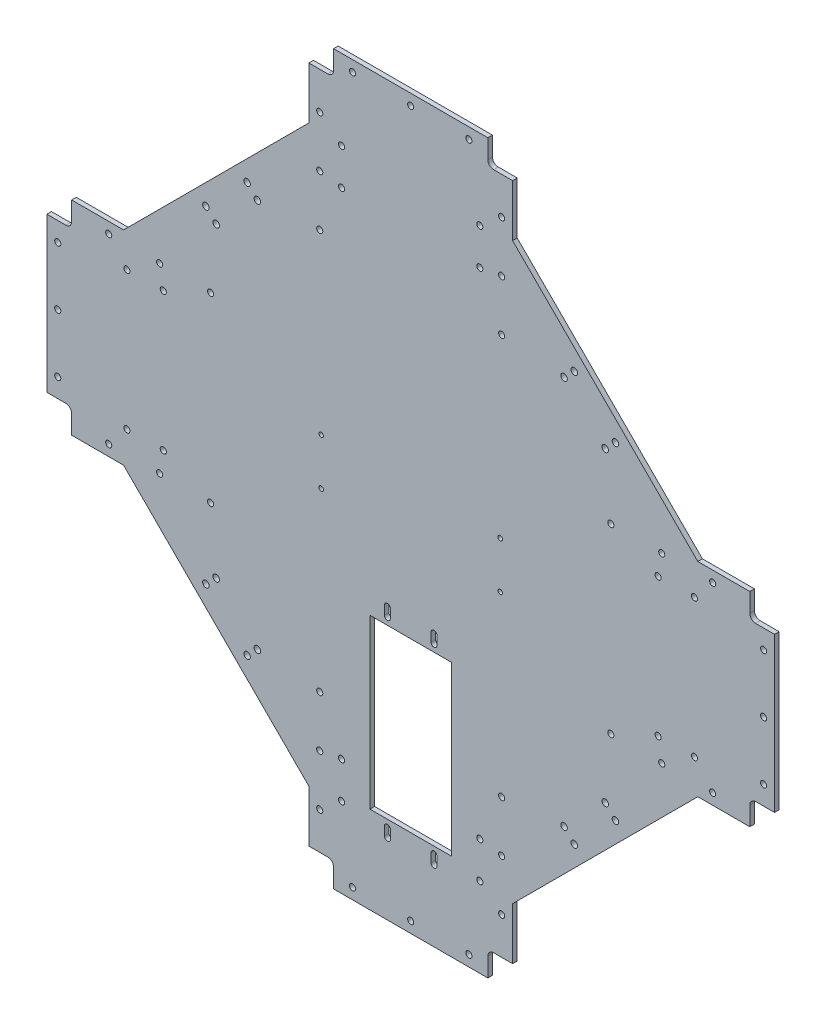
SolidWorks part; units mm, degrees
ref_plane "Front Plane" through (0, 0, 0) normal (0, 0, 1) x (1, 0, 0)
ref_plane "Top Plane" through (0, 0, 0) normal (0, 1, 0) x (1, 0, 0)
ref_plane "Right Plane" through (0, 0, 0) normal (1, 0, 0) x (0, 0, -1)
sketch "Sketch1" plane through (0, 0, 0) normal (0, 0, 1) x (1, 0, 0)
  line L0 (0, 0) -> (0, 180)
  line L1 (0, 180) -> (140, 180)
  line L2 (140, 180) -> (140, 0)
  line L3 (140, 0) -> (320, 0)
  line L4 (320, 0) -> (320, -140)
  line L5 (320, -140) -> (140, -140)
  line L6 (140, -140) -> (140, -320)
  line L7 (140, -320) -> (0, -320)
  line L8 (0, -320) -> (0, -140)
  line L9 (0, -140) -> (-180, -140)
  line L10 (-180, -140) -> (-180, 0)
  line L11 (-180, 0) -> (0, 0)
  line L12 (70, 180) -> (70, -320) construction
  line L13 (0, 180) -> (17, 180)
  line L14 (0, 180) -> (0, 163)
  line L15 (0, 163) -> (17, 163)
  line L16 (17, 180) -> (17, 163)
  line L17 (-180, -70) -> (320, -70) construction
  line L18 (140, 0) -> (0, -140) construction
  line L19 (0, 0) -> (140, -140) construction
  line L20 (7.5, 137.5) -> (7.5, 67.5) construction
  line L21 (140, 180) -> (123, 180)
  line L22 (140, 180) -> (140, 163)
  line L23 (140, 163) -> (123, 163)
  line L24 (123, 180) -> (123, 163)
  line L25 (-180, 0) -> (-163, 0)
  line L26 (-180, 0) -> (-180, -17)
  line L27 (-180, -17) -> (-163, -17)
  line L28 (-163, 0) -> (-163, -17)
  line L29 (-180, -140) -> (-163, -140)
  line L30 (-180, -140) -> (-180, -123)
  line L31 (-180, -123) -> (-163, -123)
  line L32 (-163, -140) -> (-163, -123)
  line L33 (320, 0) -> (303, 0)
  line L34 (320, 0) -> (320, -17)
  line L35 (320, -17) -> (303, -17)
  line L36 (303, 0) -> (303, -17)
  line L37 (320, -140) -> (303, -140)
  line L38 (320, -140) -> (320, -123)
  line L39 (320, -123) -> (303, -123)
  line L40 (303, -140) -> (303, -123)
  line L41 (140, -320) -> (123, -320)
  line L42 (140, -320) -> (140, -303)
  line L43 (140, -303) -> (123, -303)
  line L44 (123, -320) -> (123, -303)
  line L45 (0, -320) -> (17, -320)
  line L46 (0, -320) -> (0, -303)
  line L47 (0, -303) -> (17, -303)
  line L48 (17, -320) -> (17, -303)
  line L49 (22.5, 125) -> (117.5, 125) construction
  line L50 (22.5, 125) -> (22.5, 100) construction
  line L51 (22.5, 100) -> (117.5, 100) construction
  line L52 (117.5, 125) -> (117.5, 100) construction
  line L53 (30, 172.5) -> (110, 172.5) construction
  line L64 (42, -202.325) -> (98, -202.325) construction
  line L69 (42, -144.65) -> (98, -144.65)
  line L70 (42, -144.65) -> (42, -260)
  line L71 (42, -260) -> (98, -260)
  line L72 (98, -144.65) -> (98, -260)
  line L73 (51.95, -265) -> (56.05, -265) construction
  line L74 (51.95, -265) -> (51.95, -271)
  line L75 (51.95, -271) -> (56.05, -271) construction
  line L76 (56.05, -265) -> (56.05, -271)
  line L77 (88.05, -265) -> (88.05, -271)
  line L78 (83.95, -265) -> (83.95, -271)
  line L79 (88.05, -139.65) -> (88.05, -133.65)
  line L80 (83.95, -139.65) -> (83.95, -133.65)
  line L81 (51.95, -139.65) -> (51.95, -133.65)
  line L82 (56.05, -139.65) -> (56.05, -133.65)
  line L83 (8.5, -54) -> (131.5, -86) construction
  line L84 (8.5, -54) -> (131.5, -54) construction
  line L85 (8.5, -54) -> (8.5, -86) construction
  line L86 (8.5, -86) -> (131.5, -86) construction
  line L87 (131.5, -54) -> (131.5, -86) construction
  line L88 (131.5, -54) -> (8.5, -86) construction
  circle A0 centre (22.5, 125) radius 2.1
  circle A1 centre (22.5, 100) radius 2.1
  circle A2 centre (117.5, 125) radius 2.1
  circle A3 centre (117.5, 100) radius 2.1
  circle A4 centre (-100, -117.5) radius 2.1
  circle A5 centre (-125, -117.5) radius 2.1
  circle A6 centre (-100, -22.5) radius 2.1
  circle A7 centre (-125, -22.5) radius 2.1
  circle A8 centre (240, -117.5) radius 2.1
  circle A9 centre (240, -22.5) radius 2.1
  circle A10 centre (265, -22.5) radius 2.1
  circle A11 centre (265, -117.5) radius 2.1
  circle A12 centre (117.5, -265) radius 2.1
  circle A13 centre (117.5, -240) radius 2.1
  circle A14 centre (22.5, -240) radius 2.1
  circle A15 centre (22.5, -265) radius 2.1
  circle A17 centre (7.5, 137.5) radius 2.1
  circle A18 centre (7.5, 67.5) radius 2.1
  circle A19 centre (7.5, 102.5) radius 2.1
  circle A20 centre (30, 172.5) radius 2.1
  circle A21 centre (70, 172.5) radius 2.1
  circle A22 centre (110, 172.5) radius 2.1
  circle A23 centre (132.5, 67.5) radius 2.1
  circle A24 centre (132.5, 102.5) radius 2.1
  circle A25 centre (132.5, 137.5) radius 2.1
  circle A26 centre (207.5, -7.5) radius 2.1
  circle A27 centre (242.5, -7.5) radius 2.1
  circle A28 centre (277.5, -7.5) radius 2.1
  circle A29 centre (312.5, -30) radius 2.1
  circle A30 centre (312.5, -70) radius 2.1
  circle A31 centre (312.5, -110) radius 2.1
  circle A32 centre (277.5, -132.5) radius 2.1
  circle A33 centre (242.5, -132.5) radius 2.1
  circle A34 centre (207.5, -132.5) radius 2.1
  circle A35 centre (-67.5, -132.5) radius 2.1
  circle A36 centre (-102.5, -132.5) radius 2.1
  circle A37 centre (-137.5, -132.5) radius 2.1
  circle A38 centre (-172.5, -110) radius 2.1
  circle A39 centre (-172.5, -70) radius 2.1
  circle A40 centre (-172.5, -30) radius 2.1
  circle A41 centre (-137.5, -7.5) radius 2.1
  circle A42 centre (-102.5, -7.5) radius 2.1
  circle A43 centre (-67.5, -7.5) radius 2.1
  circle A44 centre (7.5, -207.5) radius 2.1
  circle A45 centre (7.5, -242.5) radius 2.1
  circle A46 centre (7.5, -277.5) radius 2.1
  circle A47 centre (30, -312.5) radius 2.1
  circle A48 centre (70, -312.5) radius 2.1
  circle A49 centre (110, -312.5) radius 2.1
  circle A50 centre (132.5, -277.5) radius 2.1
  circle A51 centre (132.5, -242.5) radius 2.1
  circle A52 centre (132.5, -207.5) radius 2.1
  arc A53 (51.95, -265) -> (56.05, -265) centre (54, -265) cw
  arc A54 (51.95, -271) -> (56.05, -271) centre (54, -271) ccw
  arc A55 (88.05, -271) -> (83.95, -271) centre (86, -271) cw
  arc A56 (88.05, -265) -> (83.95, -265) centre (86, -265) ccw
  arc A57 (88.05, -133.65) -> (83.95, -133.65) centre (86, -133.65) ccw
  arc A58 (88.05, -139.65) -> (83.95, -139.65) centre (86, -139.65) cw
  arc A59 (51.95, -133.65) -> (56.05, -133.65) centre (54, -133.65) cw
  arc A60 (51.95, -139.65) -> (56.05, -139.65) centre (54, -139.65) ccw
  circle A61 centre (8.5, -54) radius 1.55
  circle A62 centre (131.5, -54) radius 1.55
  circle A63 centre (131.5, -86) radius 1.55
  circle A64 centre (8.5, -86) radius 1.55
  point P21 (70, -320)
  point P24 (320, -70)
  point P147 (70, -144.65)
  point P197 (70, -70)
  point P198 (70, -70)
  dimension "D29" = 4.2
  dimension "D30" = 4.2
  dimension "D31" = 4.2
  dimension "D32" = 4.2
  dimension "D33" = 4.2
  dimension "D34" = 4.2
  dimension "D35" = 4.2
  dimension "D42" = 4.2
  dimension "D43" = 4.2
  dimension "D44" = 4.2
  dimension "D59" = 3.1
  dimension "D60" = 3.1
  dimension "D61" = 3.1
  dimension "D62" = 3.1
  dimension "D1" = 140
  dimension "D2" = 140
  dimension "D3" = 140
  dimension "D4" = 140
  dimension "D5" = 180
  dimension "D6" = 180
  dimension "D7" = 180
  dimension "D8" = 180
  dimension "D9" = 17
  dimension "D10" = 17
  dimension "D11" = 17
  dimension "D12" = 17
  dimension "D13" = 17
  dimension "D14" = 17
  dimension "D15" = 17
  dimension "D16" = 17
  dimension "D17" = 17
  dimension "D18" = 17
  dimension "D19" = 17
  dimension "D20" = 17
  dimension "D21" = 17
  dimension "D22" = 17
  dimension "D23" = 17
  dimension "D24" = 17
  dimension "D25" = 95
  dimension "D26" = 25
  dimension "D27" = 22.5
  dimension "D28" = 55
  dimension "D36" = 42.5
  dimension "D37" = 70
  dimension "D38" = 7.5
  dimension "D39" = 80
  dimension "D40" = 30
  dimension "D41" = 7.5
  dimension "D49" = 56
  dimension "D51" = 20
  dimension "D52" = 115.35
  dimension "D53" = 5
  dimension "D54" = 16
  dimension "D55" = 4.1
  dimension "D56" = 6
  dimension "D57" = 123
  dimension "D58" = 32
extrude "Boss-Extrude1" add sketch "Sketch1" along normal blind 3.175 contours L48 L7 L44 L43 L6 L5 L40 L39 L4 L35 L36 L3 L2 L23 L24 L1 L16 L15 L0 L11 L28 L27 L10 L31 L32 L9 L8 L47 A52 A51 A50 A48 A46 A44 A42 A40 A38 A37 A36 region at (70, -62.0997, 0)
fillet "Fillet1" radius 4 12 edges at (17, 163, 1.5875) (0, 0, 1.5875) (-163, -17, 1.5875) (-163, -123, 1.5875) (0, -140, 1.5875) (17, -303, 1.5875) (123, -303, 1.5875) (140, -140, 1.5875) (303, -123, 1.5875) (303, -17, 1.5875) (140, 0, 1.5875) (123, 163, 1.5875)
ref_point "Point1"
ref_plane "Plane1" through (0, 0, 0) normal (0, 0, 1) x (0, -1, 0)
sketch "Sketch10" plane through (0, 0, 0) normal (0, 0, 1) x (1, 0, 0)
  line L0 (-127.2792, -140) -> (0, -267.2792)
  line L1 (-4, -140) -> (-163, -140) construction
  line L2 (0, -1.7463) -> (0, 1.7463) construction
  line L4 (0, -140) -> (-63.6396, -203.6396) construction
  line L6 (-127.2792, -140) -> (0, -140)
  line L7 (0, -140) -> (0, -267.2792)
  line L8 (-70.7107, -182.4264) -> (-42.4264, -210.7107) construction
  circle A0 centre (-70.7107, -182.4264) radius 2.25
  circle A1 centre (-42.4264, -210.7107) radius 2.25
  circle A2 centre (-63.6396, -175.3553) radius 2.25
  circle A3 centre (-35.3553, -203.6396) radius 2.25
  point P11 (-56.5685, -196.5685)
  dimension "D6" = 2
  dimension "D4" = 4.5
  dimension "D1" = 90
  dimension "D2" = 45
  dimension "D3" = 40
  dimension "D5" = 10
  dimension "D7" = 10
extrude "Boss-Extrude2" add sketch "Sketch10" along normal blind 3.175
ref_axis "Axis1" through (70, -70, 0) along (0, 0, 1)
pattern_circular "CirPattern4" count 4 every 90 about axis through (70, -70, 0) along (0, 0, 1) of "Boss-Extrude2"
